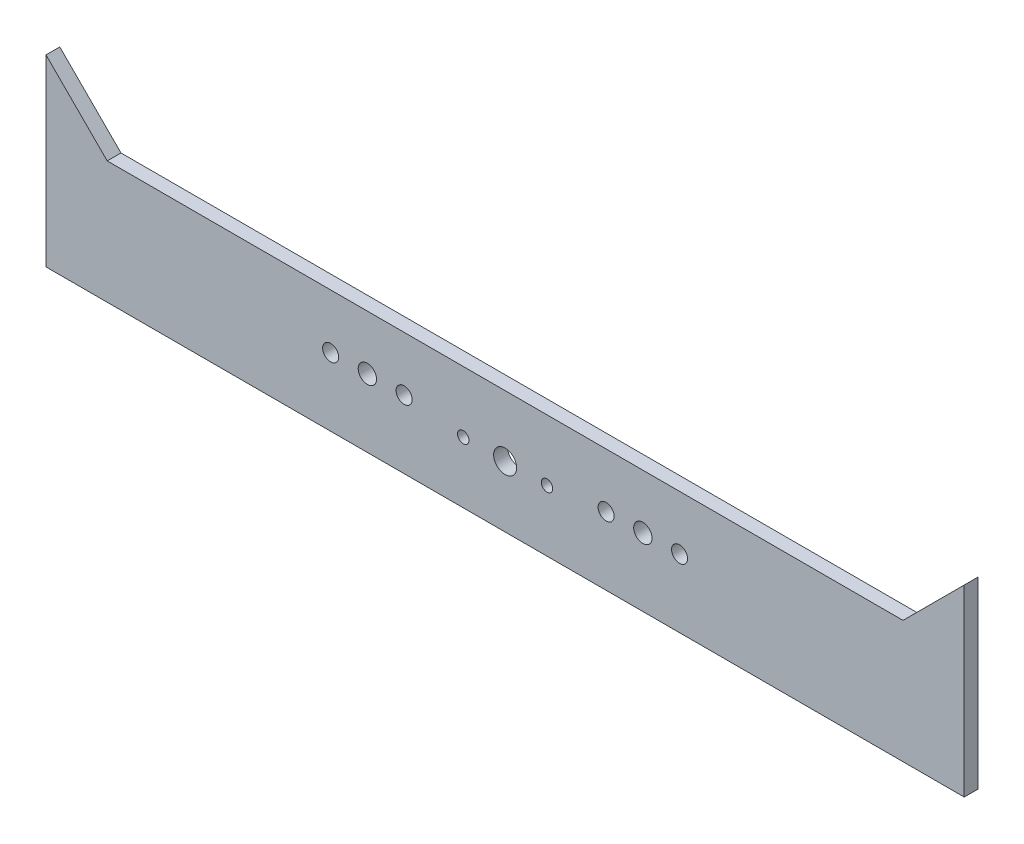
SolidWorks part; units mm, degrees
material "Wrought Stainless Steel"
ref_plane "Front Plane" through (0, 0, 0) normal (0, 0, 1) x (1, 0, 0)
ref_plane "Top Plane" through (0, 0, 0) normal (0, 1, 0) x (1, 0, 0)
ref_plane "Right Plane" through (0, 0, 0) normal (1, 0, 0) x (0, 0, -1)
sketch "Sketch1" plane through (0, 0, 0) normal (0, 0, 1) x (1, 0, 0)
  line L0 (0, -1000) -> (0, 49000) construction
  line L1 (-1000, 0) -> (49000, 0) construction
  line L2 (-1173.1632, 53.3333) -> (48826.8368, 53.3333) construction
  line L3 (-200, 0) -> (200, 0)
  line L4 (-200, 0) -> (-200, 80)
  line L6 (200, 0) -> (200, 80)
  line L7 (200, 80) -> (173.3333, 53.3333)
  line L8 (-200, 80) -> (-173.3333, 53.3333)
  line L9 (-173.3333, 53.3333) -> (173.3333, 53.3333)
  dimension "D1" = 26.6667
  dimension "D2" = 400
  dimension "D3" = 80
  dimension "D5" = 45
extrude "Boss-Extrude1" add sketch "Sketch1" along normal blind 6
sketch "Sketch2" plane through (0, 0, 6) normal (0, 0, 1) x (1, 0, 0)
  line L0 (0, -1000) -> (0, 49000) construction
  line L1 (-1200, 26.665) -> (48800, 26.665) construction
  line L4 (-200, 0) -> (200, 0) construction
  line L5 (44, 29.665) -> (76, 29.665) construction
  circle A0 centre (0, 26.665) radius 5
  circle A5 centre (60, 29.665) radius 4
  circle A6 centre (76, 29.665) radius 3.5
  circle A7 centre (44, 29.665) radius 3.5
  circle A8 centre (-44, 29.665) radius 3.5
  circle A9 centre (-76, 29.665) radius 3.5
  circle A10 centre (-60, 29.665) radius 4
  circle A11 centre (18.25, 26.665) radius 2.5
  circle A12 centre (-18.25, 26.665) radius 2.5
  point P22 (60, 29.665)
  dimension "D1" = 10
  dimension "D8" = 8
  dimension "D10" = 7
  dimension "D11" = 7
  dimension "D3" = 5
  dimension "D2" = 26.665
  dimension "D4" = 18.25
  dimension "D6" = 3
  dimension "D7" = 60
  dimension "D9" = 32
extrude "Cut-Extrude1" cut sketch "Sketch2" against normal through all
